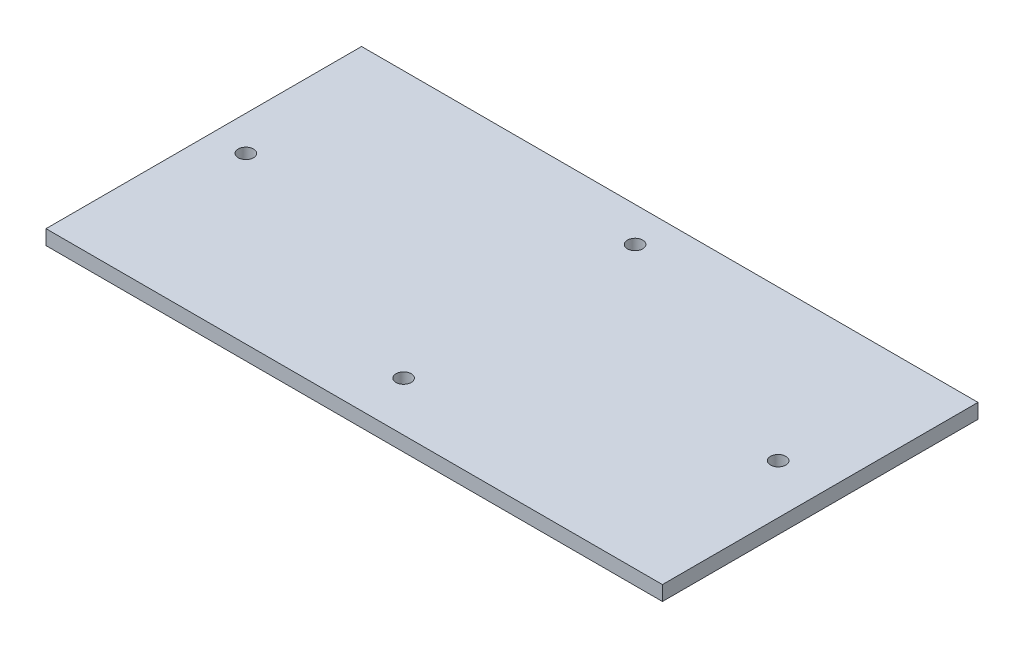
SolidWorks part; units mm, degrees
ref_plane "Front Plane" through (0, 0, 0) normal (0, 0, 1) x (1, 0, 0)
ref_plane "Top Plane" through (0, 0, 0) normal (0, 1, 0) x (1, 0, 0)
ref_plane "Right Plane" through (0, 0, 0) normal (1, 0, 0) x (0, 0, -1)
sketch "Sketch1" plane through (0, 0, 0) normal (0, 1, 0) x (1, 0, 0)
  line L0 (0, 34.0875) -> (0, -34.0875) construction
  line L1 (-66.5875, 34.0875) -> (66.5875, 34.0875)
  line L2 (-66.5875, 34.0875) -> (-66.5875, -34.0875)
  line L3 (-66.5875, -34.0875) -> (66.5875, -34.0875)
  line L4 (66.5875, 34.0875) -> (66.5875, -34.0875)
  line L5 (-66.5875, 34.0875) -> (66.5875, -34.0875) construction
  line L6 (-66.5875, -34.0875) -> (66.5875, 34.0875) construction
  line L7 (-59.0875, 26.5875) -> (55.9125, 26.5875) construction
  line L8 (-59.0875, 26.5875) -> (-59.0875, -23.4125) construction
  line L9 (-59.0875, -23.4125) -> (55.9125, -23.4125) construction
  line L10 (55.9125, 26.5875) -> (55.9125, -23.4125) construction
  line L11 (-66.5875, 0) -> (66.5875, 0) construction
  circle A0 centre (0, 26.5875) radius 1.65
  circle A1 centre (-59.0875, 1.5875) radius 1.65
  circle A2 centre (55.9125, 1.5875) radius 1.65
  circle A3 centre (0, -23.4125) radius 1.65
  point P0 (0, 0)
  point P6 (0, 0)
  point P23 (0, 0)
  point P24 (0, 0)
  dimension "D7" = 3.3
  dimension "D1" = 133.175
  dimension "D2" = 7.5
  dimension "D3" = 7.5
  dimension "D4" = 10.675
  dimension "D5" = 10.675
  dimension "D6" = 68.175
extrude "Boss-Extrude1" add sketch "Sketch1" along normal blind 3.175
